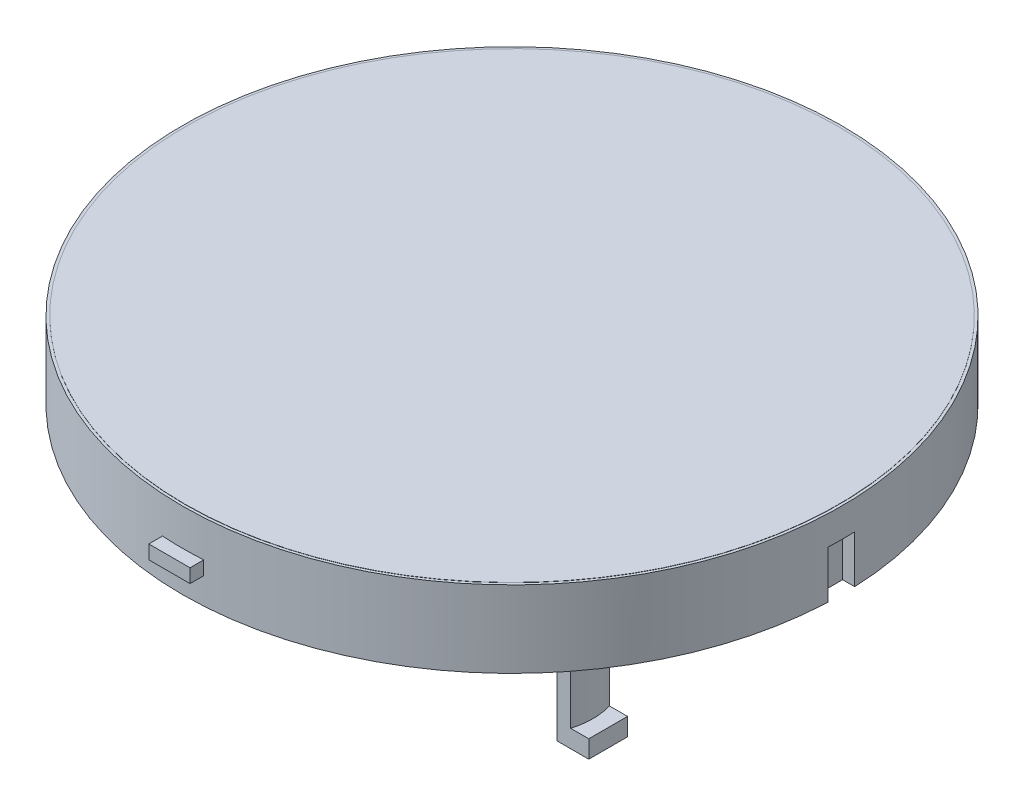
SolidWorks part; units mm, degrees
note: The reader was unsure of these and kept them because the rebuilt part matched: shared geometry of "Sketch7<2>".
material "Polybutadiene (PB)"
ref_plane "Front Plane" through (0, 0, 0) normal (0, 0, 1) x (1, 0, 0)
ref_plane "Top Plane" through (0, 0, 0) normal (0, 1, 0) x (1, 0, 0)
ref_plane "Right Plane" through (0, 0, 0) normal (1, 0, 0) x (0, 0, -1)
sketch "Sketch1" plane through (0, 0, 0) normal (0, 1, 0) x (1, 0, 0)
  circle A0 centre (0, 0) radius 37.7698
  circle A1 centre (0, 0) radius 36.322
  dimension "D1" = 75.5396
extrude "Boss-Extrude1" add sketch "Sketch1" along normal blind 8.7884
sketch "Sketch2" plane through (0, 0, 0) normal (0, 1, 0) x (1, 0, 0)
  circle A0 centre (0, 0) radius 37.7698
  dimension "D1" = 75.5396
extrude "Boss-Extrude2" add sketch "Sketch2" along normal blind 1.5494
sketch "Sketch3" plane through (0, 0, 0) normal (0, -1, 0) x (1, 0, 0)
  line L0 (-40.4636, 0) -> (45.8964, 0) construction
  line L1 (-36.3474, 1.5367) -> (-36.3474, -1.5367)
  line L2 (-36.3474, -1.5367) -> (-37.7698, -1.5367)
  line L3 (-37.7698, -1.5367) -> (-37.7698, 1.5367)
  line L4 (-37.7698, 1.5367) -> (-36.3474, 1.5367)
  line L5 (-36.3474, 1.5367) -> (-36.4442, 1.3191)
  line L6 (36.3474, 1.5367) -> (37.7952, 1.5367)
  line L7 (36.3474, -1.5367) -> (36.3474, 1.5367)
  line L8 (37.7952, -1.5367) -> (36.3474, -1.5367)
  line L9 (37.7952, 1.5367) -> (37.7952, -1.5367)
  circle A0 centre (0, 0) radius 5.7277
  dimension "D1" = 11.4554
extrude "Cut-Extrude1" cut sketch "Sketch3" against normal blind 5.461
sketch "Sketch4" plane through (0, 0, 0) normal (0, -1, 0) x (1, 0, 0)
  line L0 (0, 40.0507) -> (0, -41.7023) construction
  line L1 (-2.3622, -39.2729) -> (2.3622, -39.2729)
  line L2 (2.3622, -39.2729) -> (2.3622, -37.7489)
  line L3 (-2.3622, 37.7372) -> (-2.3622, 37.51)
  line L4 (-2.3622, 37.51) -> (2.3622, 37.51)
  line L5 (-2.3622, 37.7372) -> (2.3622, 37.7372) construction
  line L6 (2.3622, 39.2612) -> (-2.3622, 39.2612)
  line L7 (2.3622, 37.7372) -> (2.3622, 39.2612)
  line L8 (-2.3622, 39.2612) -> (-2.3622, 37.7372)
  line L9 (-2.3622, -39.2729) -> (-2.3622, -37.2494)
  line L10 (-2.3622, -37.2494) -> (2.3622, -37.2494)
  line L11 (2.3622, -37.2494) -> (2.3622, -37.7489)
  line L12 (2.3622, 37.51) -> (2.3622, 37.7372)
extrude "Boss-Extrude3" add sketch "Sketch4" against normal blind 1.5748 from offset 3.0226 offset against normal yes
sketch "Sketch5" plane through (0, 0, 0) normal (0, -1, 0) x (1, 0, 0)
  circle A0 centre (0, 0) radius 9.271
  dimension "D1" = 18.542
extrude "Extrude-Thin1" add sketch "Sketch5" along normal blind 15.4686 thin thin type one direction reverse wall 1.5748
sketch "Sketch6" plane through (0, -15.4686, 0) normal (0, -1, 0) x (1, 0, 0)
  line L0 (-44.1008, 0) -> (49.8913, 0) construction
  line L1 (7.747, 2.2225) -> (8.9358, 2.2225)
  line L2 (7.3683, 2.2225) -> (7.747, 2.2225)
  line L3 (8.9358, -2.2225) -> (7.3683, -2.2225)
  line L5 (-8.9358, 2.2225) -> (-7.3683, 2.2225)
  line L6 (-8.9358, 2.2225) -> (-7.747, 2.2225)
  line L7 (-7.747, -2.2225) -> (-8.9358, -2.2225)
  line L10 (-7.3683, -2.2225) -> (-7.747, -2.2225)
  arc A0 (-8.9358, 2.2225) -> (-8.9358, -2.2225) centre (-1.7359, 0) ccw
  arc A1 (-7.3683, 2.2225) -> (-7.3683, -2.2225) centre (0, 0) ccw
  arc A2 (7.3683, -2.2225) -> (7.3683, 2.2225) centre (0, 0) ccw
  circle A3 centre (0, 0) radius 7.6962 construction
  circle A4 centre (0, 0) radius 7.6962 construction
  arc A5 (8.9358, -2.2225) -> (8.9358, 2.2225) centre (1.7359, 0) ccw
  circle M2 centre (0, 0) radius 7.6962
  dimension "D1" = 7.5351
  dimension "D2" = 7.6962
extrude "Boss-Extrude4" add sketch "Sketch6" along normal blind 13.1318 contours A0 L0 A1 L5 | L0 A0 L7 L10 M2 | L0 A5 L1 L2 M2 | L0 A2 L3 A5
chamfer "Chamfer2" distance 2.54 angle 45 1 edges
sketch "Sketch7" plane through (0, 0, 0) normal (1, 0, 0) x (0, 0, -1)
  line L0 (2.2225, -28.6004) -> (2.2225, -14.4404) construction
  line L1 (2.2225, -26.5684) -> (-2.2225, -26.5684)
  line L2 (2.2225, -26.5684) -> (2.2225, -28.6004)
  line L3 (2.2225, -28.6004) -> (-2.2225, -28.6004)
  line L4 (-2.2225, -26.5684) -> (-2.2225, -28.6004)
extrude "Boss-Extrude5" add sketch "Sketch7" against normal blind 2.0828 from vertex at -8.9358 starting at point (-8.9358, -28.6004, 2.2225)
extrude "Boss-Extrude6" add sketch "Sketch7<2>" along normal blind 2.0828 from vertex at 8.9358 starting at point (8.9358, -28.6004, -2.2225)
sketch "Sketch7<2>" plane through (0, 0, 0) normal (1, 0, 0) x (0, 0, -1) same geometry as "Sketch7"
chamfer "Chamfer4" distance 2.54 angle 45 1 edges
sketch "Sketch8" plane through (0, 8.7884, 0) normal (0, 1, 0) x (1, 0, 0)
  circle A0 centre (0, 0) radius 37.465
  dimension "D1" = 74.93
extrude "Boss-Extrude7" add sketch "Sketch8" along normal blind 0.0254
